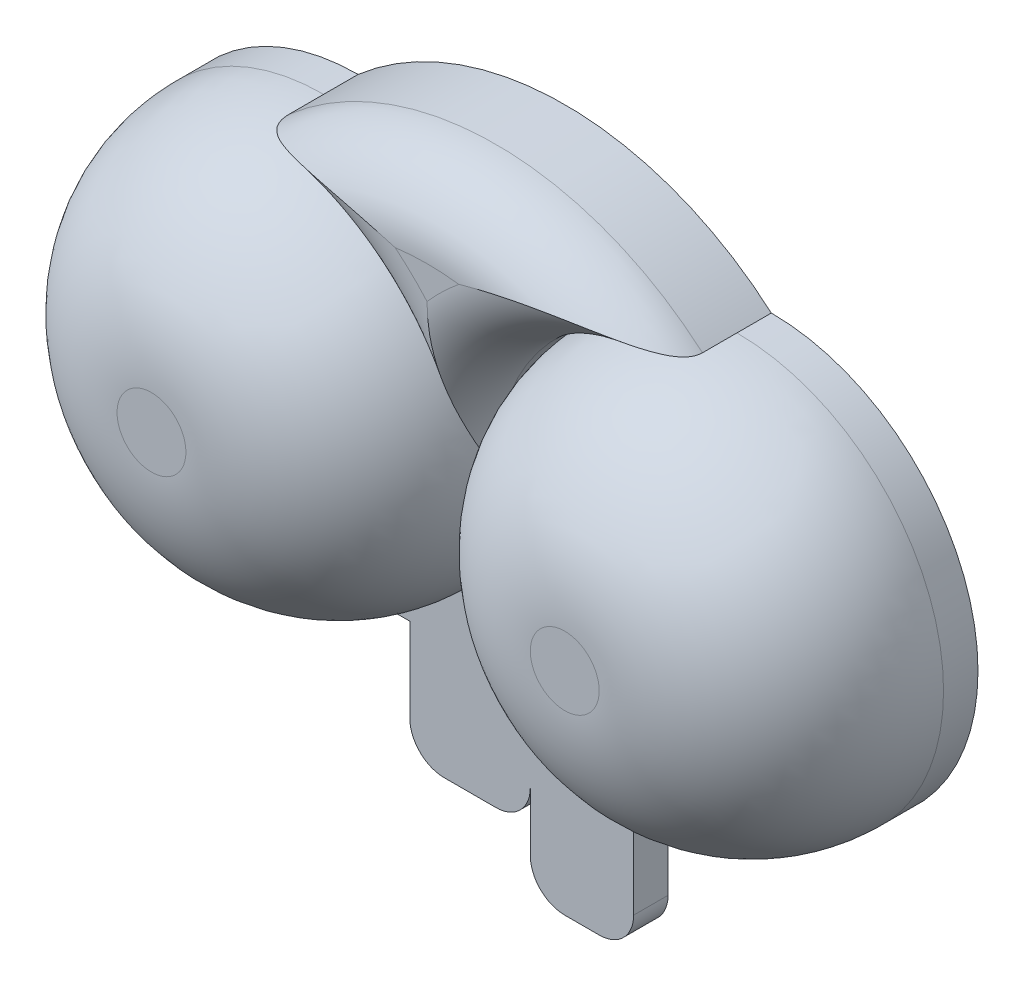
SolidWorks part; units mm, degrees
ref_plane "Plan de face" through (0, 0, 0) normal (0, 0, 1) x (1, 0, 0)
ref_plane "Plan de dessus" through (0, 0, 0) normal (0, 1, 0) x (1, 0, 0)
ref_plane "Plan de droite" through (0, 0, 0) normal (1, 0, 0) x (0, 0, -1)
sketch "Esquisse1" plane through (0, 0, 0) normal (0, 0, 1) x (1, 0, 0)
  line L0 (0, 0) -> (12, 0) construction
  circle A0 centre (0, 0) radius 6
  circle A1 centre (12, 0) radius 6
  dimension "D2" = 12
  dimension "D3" = 12
  dimension "D1" = 12
extrude "Boss.-Extru.2" add sketch "Esquisse1" along normal blind 6 contours A0 | A1 region at (0, 0, 0) region at (12, 0, 0)
fillet "Congé2" radius 5 1 edges at (6, 0, 6)
fillet "Congé3" radius 5 1 edges at (18, 0, 6)
sketch "Esquisse4" plane through (0, 0, 0) normal (0, 0, -1) x (-1, 0, 0)
  line L4 (0, 0) -> (-12, 0) construction
  line L5 (0, -6) -> (-12, -6)
  line L6 (0, 6) -> (-12, 6)
  arc A4 (0, -6) -> (0, 6) centre (0, 0) ccw
  arc A5 (-12, 6) -> (-12, -6) centre (-12, 0) ccw
  point P2 (-6, 0)
  dimension "D1" = 12
extrude "Boss.-Extru.9" add sketch "Esquisse4" against normal blind 1
sketch "Esquisse5" plane through (0, 0, 1) normal (0, 0, 1) x (1, 0, 0)
  line L5 (12, 6) -> (0, 6)
  arc A8 (0, 6) -> (12, 6) centre (6, -0.9037) cw
  arc A10 (6, 0) -> (0, 6) centre (0, 0) ccw
  arc A11 (12, 6) -> (6, 0) centre (12, 0) ccw
  arc A12 (6, 0) -> (0, 6) centre (0, 0) ccw
  arc A13 (12, 6) -> (6, 0) centre (12, 0) ccw
  dimension "D1" = 0
extrude "Boss.-Extru.10" add sketch "Esquisse5" along normal blind 3
fillet "Congé4" radius 2 3 edges at (6, 8.2429, 4) (7.7574, 4.2426, 4) (4.2426, 4.2426, 4)
sketch "Esquisse6" plane through (0, 0, 1) normal (0, 0, -1) x (-1, 0, 0)
  line L2 (-12, 6) -> (0, 6)
  line L3 (-12, 6) -> (0, 6)
  arc A2 (0, 6) -> (-12, 6) centre (-6, -0.9037) ccw
  arc A3 (0, 6) -> (-12, 6) centre (-6, -0.9037) ccw
  dimension "D1" = 0
extrude "Boss.-Extru.11" add sketch "Esquisse6" along normal blind 1
sketch "Esquisse7" plane through (0, 0, 1) normal (0, 0, 1) x (1, 0, 0)
  line L1 (6, 0) -> (2.5, 0)
  line L2 (6, 0) -> (6, -8.4357)
  line L3 (5, -9.4357) -> (3.5, -9.4357)
  line L4 (2.5, 0) -> (2.5, -8.4357)
  line L5 (6, 0) -> (9, 0)
  line L6 (6, 0) -> (6, -10.1424)
  line L7 (7, -11.1424) -> (8, -11.1424)
  line L8 (9, 0) -> (9, -10.1424)
  arc A0 (6, 0) -> (12, -6) centre (12, 0) ccw construction
  arc A1 (0, -6) -> (6, 0) centre (0, 0) ccw construction
  arc A2 (9, -10.1424) -> (8, -11.1424) centre (8, -10.1424) cw
  arc A3 (6, -10.1424) -> (7, -11.1424) centre (7, -10.1424) ccw
  arc A4 (6, -8.4357) -> (5, -9.4357) centre (5, -8.4357) cw
  arc A5 (3.5, -9.4357) -> (2.5, -8.4357) centre (3.5, -8.4357) cw
  point P15 (9, -11.1424)
  point P18 (6, -11.1424)
  point P21 (6, -9.4357)
  point P24 (2.5, -9.4357)
  line M13 (0, -6) -> (12, -6)
  dimension "D3" = 1
  dimension "D1" = 3.5
  dimension "D2" = 3
extrude "Boss.-Extru.14" add sketch "Esquisse7" against normal blind 1 contours A5 L3 A4 L2 L4 M13 | L6 A3 L7 A2 L8 L2 M13 region at (7.5, -8.504, 1) region at (4.25, -7.6625, 1)
